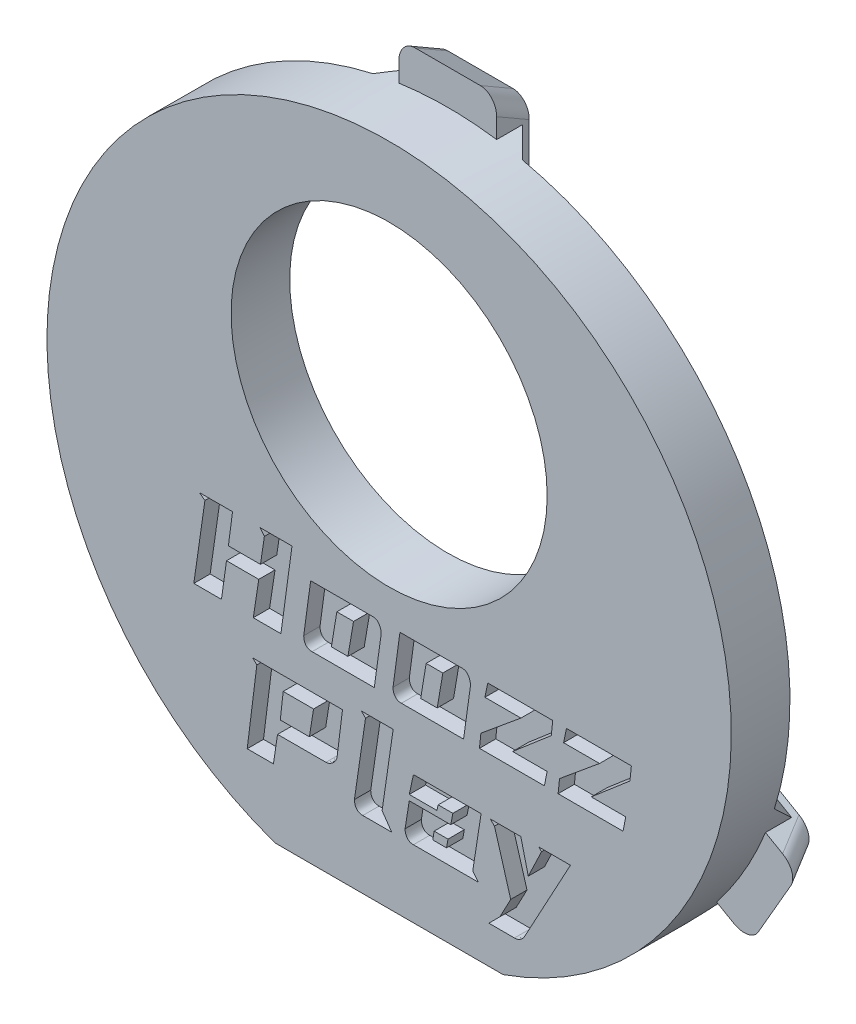
SolidWorks part; units mm, degrees
ref_plane "前视基准面" through (0, 0, 0) normal (0, 0, 1) x (1, 0, 0)
ref_plane "上视基准面" through (0, 0, 0) normal (0, 1, 0) x (1, 0, 0)
ref_plane "右视基准面" through (0, 0, 0) normal (1, 0, 0) x (0, 0, -1)
sketch "草图1" plane through (0, 0, 0) normal (0, 0, 1) x (1, 0, 0)
  circle A0 centre (0, 0) radius 10.5
  dimension "D1" = 21
extrude "凸台-拉伸1" add sketch "草图1" along normal blind 1.8
sketch "草图2" plane through (0, 0, 0) normal (0, 0, 1) x (1, 0, 0)
  circle A0 centre (0, 3.5) radius 4.85
  circle A1 centre (0, 0) radius 10.5 construction
  point P2 (0, 10.5)
  point P3 (0, 8.35)
  dimension "D1" = 9.7
  dimension "D2" = 7
extrude "切除-拉伸4" cut sketch "草图2" along normal blind 2 and the other way through all
sketch "草图3" plane through (0, 0, 0) normal (0, 0, 1) x (1, 0, 0)
  line L0 (-3.5, -9.9) -> (3.5, -9.9)
  line L1 (3.5, -9.9) -> (3.5, -10.9)
  line L2 (3.5, -10.9) -> (-3.5, -10.9)
  line L3 (-3.5, -10.9) -> (-3.5, -9.9)
  point P11 (0, -9.9)
  dimension "D1" = 7
  dimension "D2" = 9.9
  dimension "D3" = 1
extrude "切除-拉伸5" cut sketch "草图3" along normal through all both and the other way through all
sketch "草图4" plane through (0, 0, 0) normal (0, 0, 1) x (1, 0, 0)
  line L1 (-1.5, 12) -> (1.5, 12)
  line L2 (-1.5, 12) -> (-1.5, 9)
  line L3 (-1.5, 9) -> (1.5, 9)
  line L4 (1.5, 12) -> (1.5, 9)
  line L5 (-1.5, 12) -> (1.5, 9) construction
  line L6 (-1.5, 9) -> (1.5, 12) construction
  arc A0 (3.4986, -9.9) -> (-3.4986, -9.9) centre (0, 0) ccw construction
  point P0 (0, 10.5)
  dimension "D1" = 3
  dimension "D2" = 3
extrude "凸台-拉伸2" add sketch "草图4" against normal blind 1
pattern_circular "阵列(圆周)1" count 3 every 120 about axis through (0, 0, 1.8) along (0, 0, 1) of "凸台-拉伸2"
chamfer "倒角1" distance 1 angle 60 3 edges at (0, 12, -1) (-10.3923, -6, -1) (10.3923, -6, -1) first distance on face at (0, 10.5, -1) first distance on face at (-9.0933, -5.25, -1) first distance on face at (9.0933, -5.25, -1)
fillet "圆角1" radius 0.5 6 edges at (-9.0263, -6.9434, -0.5) (-10.5263, -4.3453, -0.5) (-1.5, 11.2887, -0.5) (1.5, 11.2887, -0.5) (9.0263, -6.9434, -0.5) (10.5263, -4.3453, -0.5)
chamfer "倒角2" distance 0.8 angle 45 9 edges at (-1.5, 9.6962, 0) (0, 9, 0) (1.5, 9.6962, 0) (9.1471, -3.549, 0) (7.7942, -4.5, 0) (7.6471, -6.1471, 0) (-7.6471, -6.1471, 0) (-7.7942, -4.5, 0) (-9.1471, -3.549, 0)
sketch "草图5" plane through (0, 0, 1.8) normal (0, 0, 1) x (1, 0, 0)
  text T0 "Hoozz" font "@优设标题黑" height 2.5
  text T1 "Play" font "@优设标题黑" height 2.5
extrude "切除-拉伸6" cut sketch "草图5" against normal blind 0.5
